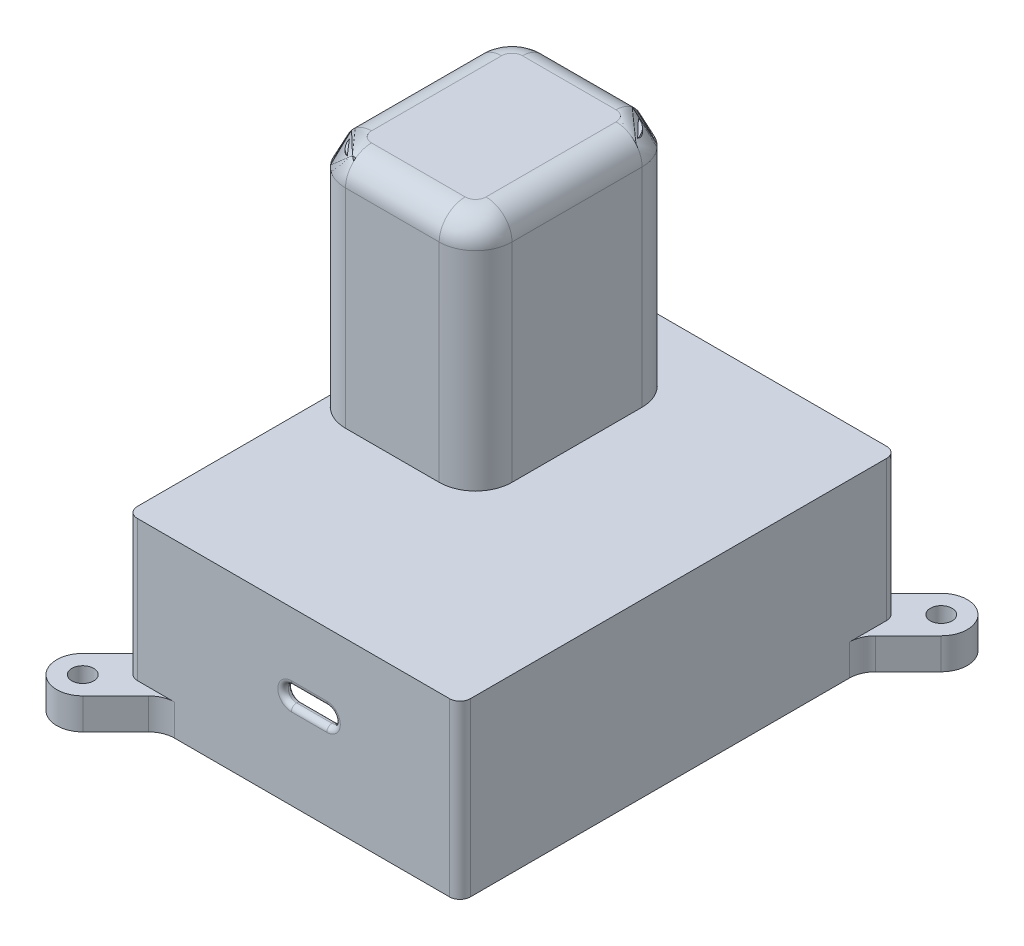
SolidWorks part; units mm, degrees
ref_plane "Front Plane" through (0, 0, 0) normal (0, 0, 1) x (1, 0, 0)
ref_plane "Top Plane" through (0, 0, 0) normal (0, 1, 0) x (1, 0, 0)
ref_plane "Right Plane" through (0, 0, 0) normal (1, 0, 0) x (0, 0, -1)
sketch "Sketch1" plane through (0, 0, 0) normal (0, 1, 0) x (1, 0, 0)
  line L0 (0, 0) -> (60, 0)
  line L1 (60, 0) -> (60, -80)
  line L2 (60, -80) -> (0, -80)
  line L3 (0, -80) -> (0, 0)
  line L4 (-2, -82) -> (-2, 2)
  line L5 (-2, 2) -> (62, 2)
  line L6 (62, 2) -> (62, -82)
  line L7 (62, -82) -> (-2, -82)
  dimension "D1" = 60
  dimension "D2" = 80
  dimension "D3" = 2
extrude "Boss-Extrude1" add sketch "Sketch1" along normal blind 30
ref_plane "HOLE_MIRROR_PLANE" through (-0.3013, 0, 0.2296) normal (0.7954, 0, -0.606) x (-0.606, 0, -0.7954)
sketch "Sketch2" plane through (0, 0, 0) normal (0, 1, 0) x (1, 0, 0)
  line L0 (-2, -82) -> (-6.2426, -86.2426) construction
  line L1 (62, 2) -> (66.2426, 6.2426) construction
  line L2 (69.7782, 2.7071) -> (62, -5.0711)
  line L3 (62.7071, 2.7071) -> (69.7782, 2.7071)
  line L4 (62, -82) -> (62, 2) construction
  line L5 (62, -5.0711) -> (60, 0)
  line L7 (66.2426, 6.2426) -> (69.7782, 2.7071) construction
  line L8 (66.2426, 6.2426) -> (62.8613, 9.9259) construction
  line L9 (62, 2) -> (-2, 2) construction
  line L10 (54.9289, 2) -> (62.8613, 9.9259)
  line L11 (62.8613, 9.9259) -> (62.7071, 2.7071)
  line L12 (60, 0) -> (54.9289, 2)
  line L13 (-6.2426, -86.2426) -> (-2.7071, -89.7782) construction
  line L14 (-6.2426, -86.2426) -> (-9.7782, -82.7071) construction
  line L15 (-2.7071, -89.7782) -> (5.0711, -82)
  line L16 (-2, -82) -> (62, -82) construction
  line L17 (5.0711, -82) -> (0, -80)
  line L18 (-9.7782, -82.7071) -> (-2, -74.9289)
  line L19 (-2, 2) -> (-2, -82) construction
  line L20 (-2, -74.9289) -> (0, -80)
  line L21 (-9.7782, -82.7071) -> (-2.7071, -82.7071)
  line L22 (-2.7071, -82.7071) -> (-2.7071, -89.7782)
  circle A6 centre (66.2426, 6.2426) radius 2.1
  circle A7 centre (66.2426, 6.2426) radius 5
  circle A8 centre (-6.2426, -86.2426) radius 2.1
  circle A9 centre (-6.2426, -86.2426) radius 5
  dimension "D3" = 4.2
  dimension "D4" = 6
  dimension "D2" = 10
  dimension "D5" = 10
  dimension "D6" = 4.2
  dimension "D1" = 6
extrude "Boss-Extrude2" add sketch "Sketch2" along normal blind 6 contours L21 A9 L22 A8 | A9 L15 L17 L20 L18 | L22 A9 | L21 A9 | A7 L10 L12 L5 L2 | L3 A7 | L10 A7 L11 | L3 A7 L11 A6 | L3 L2 L5 L12 L10 L11 region at (66.2426, 0, -2.1133) region at (61.3999, 0, -1.3971) region at (66.2426, 0, -2.8278) region at (62.159, 0, -6.3293) region at (-1.3994, 0, 81.3994) region at (-9.6928, 0, 89.6928) region at (-2.1133, 0, 86.2426) region at (-6.2426, 0, 82.1133)
ref_plane "USBC_HOLE_PLANE" through (0, 0, 82) normal (0, 0, 1) x (1, 0, 0)
sketch "Sketch4" plane through (0, 0, 82) normal (0, 0, 1) x (1, 0, 0)
  line L0 (33.0013, 0) -> (33.0013, 16.6) construction
  line L1 (5.0711, 0) -> (62, 0) construction
  line L2 (33.0013, 16.6) -> (33.0013, 18.2) construction
  line L3 (33.0013, 18.2) -> (28.0013, 18.2) construction
  line L4 (33.0013, 18.2) -> (33.0013, 19.8) construction
  line L5 (28.0013, 18.2) -> (29.6013, 18.2) construction
  line L6 (33.0013, 19.8) -> (29.6013, 19.8)
  line L7 (33.0013, 16.6) -> (29.6013, 16.6)
  line L8 (33.0013, 18.2) -> (38.0013, 18.2) construction
  line L9 (38.0013, 18.2) -> (36.4013, 18.2) construction
  line L10 (33.0013, 19.8) -> (36.4013, 19.8)
  line L11 (33.0013, 16.6) -> (36.4013, 16.6)
  arc A0 (29.6013, 16.6) -> (29.6013, 19.8) centre (29.6013, 18.2) cw
  arc A1 (36.4013, 19.8) -> (36.4013, 16.6) centre (36.4013, 18.2) cw
  dimension "D1" = 16.6
  dimension "D2" = 1.6
  dimension "D3" = 5
  dimension "D4" = 1.6
  dimension "D5" = 1.6
  dimension "D6" = 5
  dimension "D7" = 1.6
extrude "Cut-Extrude1" cut sketch "Sketch4" against normal blind 30
fillet "Fillet2" radius 1 4 edges at (28.0013, 18.2, 82) (33.0013, 19.8, 82) (38.0013, 18.2, 82) (33.0013, 16.6, 82)
fillet "Fillet7" radius 2 8 edges at (0, 15, 80) (60, 15, 80) (60, 15, 0) (0, 15, 0) (62, 15, 82) (-2, 15, -2) (-2, 18, 82) (62, 18, -2)
fillet "Fillet8" radius 1 4 edges at (38.0013, 18.2, 80) (33.0013, 19.8, 80) (28.0013, 18.2, 80) (33.0013, 16.6, 80)
fillet "Fillet9" radius 5 4 edges at (62, 3, 5.0711) (54.9289, 3, -2) (-2, 3, 74.9289) (5.0711, 3, 82)
sketch "Sketch5" plane through (0, 30, 0) normal (0, 1, 0) x (1, 0, 0)
  line L0 (-2, 0) -> (-2, -10) construction
  line L1 (-2, 0) -> (-2, -80) construction
  line L2 (-2, -10) -> (-2, -45) construction
  line L3 (-2, -45) -> (-2, -80)
  line L4 (0, -82) -> (60, -82)
  line L5 (0, -82) -> (-2, -82)
  line L6 (-2, -82) -> (-2, -80)
  line L7 (62, -80) -> (62, 0)
  line L8 (60, -82) -> (62, -82)
  line L9 (62, -82) -> (62, -80)
  line L10 (0, 2) -> (60, 2)
  line L11 (60, 2) -> (62, 2)
  line L12 (62, 2) -> (62, 0)
  line L13 (0, 2) -> (-2, 2)
  line L14 (-2, 2) -> (-2, 0)
  line L15 (-2, 0) -> (-2, -10)
  line L16 (-2, -10) -> (28, -10)
  line L17 (28, -10) -> (28, -45)
  line L18 (28, -45) -> (-2, -45)
  line L19 (-2, -10) -> (-2, -45)
  line L20 (0, -45) -> (0, -10)
  line L21 (0, -2) -> (0, -78) construction
  line L22 (0, -10) -> (-2, -10)
  line M19 (-2, 0) -> (-2, -80)
  arc M20 (-2, -80) -> (0, -82) centre (0, -80) ccw
  line M21 (0, -82) -> (60, -82)
  arc M22 (60, -82) -> (62, -80) centre (60, -80) ccw
  line M23 (62, -80) -> (62, 0)
  arc M24 (62, 0) -> (60, 2) centre (60, 0) ccw
  line M25 (60, 2) -> (0, 2)
  arc M26 (0, 2) -> (-2, 0) centre (0, 0) ccw
  line M27 (0, -78) -> (0, -2)
  arc M28 (0, -2) -> (2, 0) centre (2, -2) cw
  line M29 (2, 0) -> (58, 0)
  arc M30 (58, 0) -> (60, -2) centre (58, -2) cw
  line M31 (60, -2) -> (60, -78)
  arc M32 (60, -78) -> (58, -80) centre (58, -78) cw
  line M33 (58, -80) -> (2, -80)
  arc M34 (2, -80) -> (0, -78) centre (2, -78) cw
  dimension "D1" = 10
  dimension "D2" = 35
  dimension "D3" = 30
extrude "Boss-Extrude3" add sketch "Sketch5" along normal blind 3 contours L18 L16 M27 M19 | L17 L18 L16 M27 M34 M33 M32 M31 M30 M29 M28 | L18 L16 M27 M19 M20 M21 M22 M23 M24 M25 M26 M28 M29 M30 M31 M32 M33 M34 region at (-1, 30, 46.056) region at (-1, 30, 27.5) region at (34.1084, 30, 43.2097)
sketch "Sketch6" plane through (0, 33, 0) normal (0, 1, 0) x (1, 0, 0)
  line L0 (5, -10) -> (14, -10)
  line L1 (0, -10) -> (28, -10) construction
  line L2 (14, -10) -> (23, -10)
  line L3 (28, -15) -> (28, -40)
  line L4 (23, -45) -> (14, -45)
  line L5 (28, -45) -> (0, -45) construction
  line L6 (14, -45) -> (5, -45)
  line L7 (0, -40) -> (0, -15)
  line L12 (-2, -40) -> (-2, -15)
  line L13 (5, -8) -> (14, -8)
  line L14 (14, -8) -> (23, -8)
  line L15 (30, -15) -> (30, -40)
  line L16 (23, -47) -> (14, -47)
  line L17 (14, -47) -> (5, -47)
  arc A0 (0, -40) -> (5, -45) centre (5, -40) ccw
  arc A1 (23, -45) -> (28, -40) centre (23, -40) ccw
  arc A2 (28, -15) -> (23, -10) centre (23, -15) ccw
  arc A3 (0, -15) -> (5, -10) centre (5, -15) cw
  arc A8 (-2, -15) -> (5, -8) centre (5, -15) cw
  arc A9 (30, -15) -> (23, -8) centre (23, -15) ccw
  arc A10 (23, -47) -> (30, -40) centre (23, -40) ccw
  arc A11 (-2, -40) -> (5, -47) centre (5, -40) ccw
  point P15 (0, -45)
  point P18 (28, -45)
  point P21 (28, -10)
  point P24 (0, -10)
  dimension "D1" = 5
  dimension "D2" = 2
extrude "Boss-Extrude4" add sketch "Sketch6" along normal blind 45 and the other way blind 3
sketch "Sketch7" plane through (0, 78, 0) normal (0, 1, 0) x (1, 0, 0)
  line L0 (0, -15) -> (0, -40)
  line L1 (0, -40) -> (0.0503, -44.9497)
  line L2 (0.0503, -44.9497) -> (4.2929, -44.9497)
  line L5 (28, -40) -> (28, -15)
  line L6 (28, -15) -> (27.9497, -10.0503)
  line L7 (27.9497, -10.0503) -> (23, -10)
  line L8 (23, -10) -> (5, -10)
  line L9 (23, -10) -> (5, -10) construction
  line L12 (4.2929, -44.9497) -> (5, -45)
  line L13 (5, -45) -> (23, -45)
  line L14 (23, -45) -> (25.0123, -45)
  line L15 (25.0123, -45) -> (26.6261, -43.8962)
  line L16 (26.6261, -43.8962) -> (28, -42.9564)
  line L17 (28, -42.9564) -> (28, -40)
  line L18 (0, -15) -> (-0.2325, -13.2579)
  line L19 (-0.2325, -13.2579) -> (0.3978, -11.7488)
  line L20 (0.3978, -11.7488) -> (1.1619, -10.6982)
  line L21 (1.1619, -10.6982) -> (2.4159, -9.8405)
  line L22 (2.4159, -9.8405) -> (3.9041, -9.6419)
  line L23 (3.9041, -9.6419) -> (5, -10)
  arc A0 (-2, -40) -> (5, -47) centre (5, -40) ccw construction
  arc A1 (0, -40) -> (5, -45) centre (5, -40) ccw construction
  arc A2 (30, -15) -> (23, -8) centre (23, -15) ccw construction
  arc A3 (5, -10) -> (0, -15) centre (5, -15) ccw construction
extrude "Boss-Extrude6" add sketch "Sketch7" against normal blind 2
fillet "Fillet11" radius 5 8 edges at (14, 78, 8) (27.9497, 78, 10.0503) (30, 78, 27.5) (27.9497, 78, 44.9497) (14, 78, 47) (0.0503, 78, 44.9497) (-2, 78, 27.5) (0.0503, 78, 10.0503)
fillet "Fillet12" radius 2 9 edges at (0, 30, 6) (0.5858, 30, 0.5858) (30, 30, 0) (59.4142, 30, 0.5858) (60, 30, 40) (59.4142, 30, 79.4142) (30, 30, 80) (0.5858, 30, 79.4142) (0, 30, 61.5)
